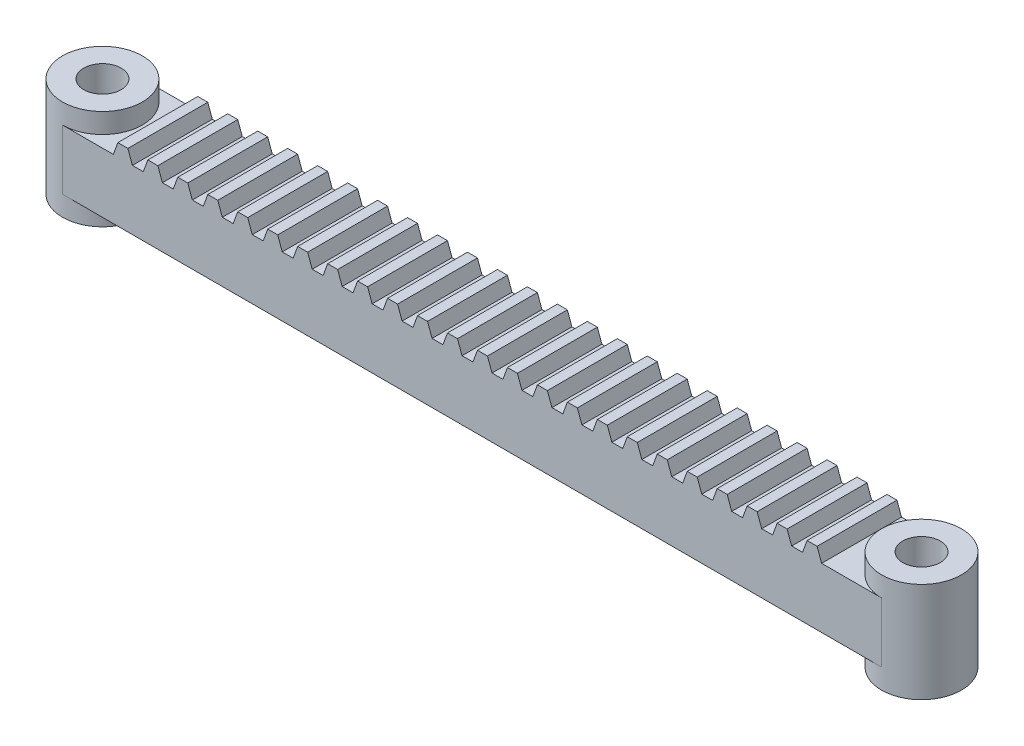
SolidWorks part; units mm, degrees
material "Galvanized Steel"
ref_plane "Front Plane" through (0, 0, 0) normal (0, 0, 1) x (1, 0, 0)
ref_plane "Top Plane" through (0, 0, 0) normal (0, 1, 0) x (1, 0, 0)
ref_plane "Right Plane" through (0, 0, 0) normal (1, 0, 0) x (0, 0, -1)
sketch "Sketch2" plane through (0, 0, 0) normal (0, 1, 0) x (1, 0, 0)
  line L0 (-82, 8) -> (82, 8)
  line L1 (-82, -8) -> (82, -8)
  line L2 (-82, 0) -> (0, 0) construction
  line L3 (0, 0) -> (82, 0) construction
  circle A0 centre (-82, 0) radius 8
  circle A1 centre (82, 0) radius 8
  circle A2 centre (-82, 0) radius 3.75
  circle A3 centre (82, 0) radius 3.75
  dimension "D1" = 16
  dimension "D3" = 7.5
  dimension "D2" = 164
extrude "Boss-Extrude1" add sketch "Sketch2" along normal mid plane 12 contours A1 L0 A0 L1 region at (0, 0, 0)
extrude "Boss-Extrude2" add sketch "Sketch2<3>" along normal mid plane 20 contours A0 A2 | A1 A3 region at (-76.5031, 0, -5.4969) region at (87.4969, 0, -5.4969)
sketch "Sketch2<3>" plane through (0, 0, 0) normal (0, 1, 0) x (1, 0, 0) same geometry as "Sketch2"
sketch "Sketch3" plane through (0, 0, 0) normal (0, 0, 1) x (1, 0, 0)
  line L0 (70, 6) -> (69.0901, 8.5)
  line L1 (-82, 6) -> (82, 6) construction
  line L2 (69.0901, 8.5) -> (67.0901, 8.5)
  line L3 (67.0901, 8.5) -> (66.1801, 6)
  line L4 (66.1801, 6) -> (70, 6)
  point P4 (68.0901, 8.5)
  point P7 (68.0901, 6)
  dimension "D1" = 2
  dimension "D2" = 20
  dimension "D3" = 40
  dimension "D4" = 2.5
extrude "Boss-Extrude3" add sketch "Sketch3" along normal mid plane 16
pattern_linear "LPattern1" count 24 spacing 6 along (-1, 0, 0) of "Boss-Extrude3"
